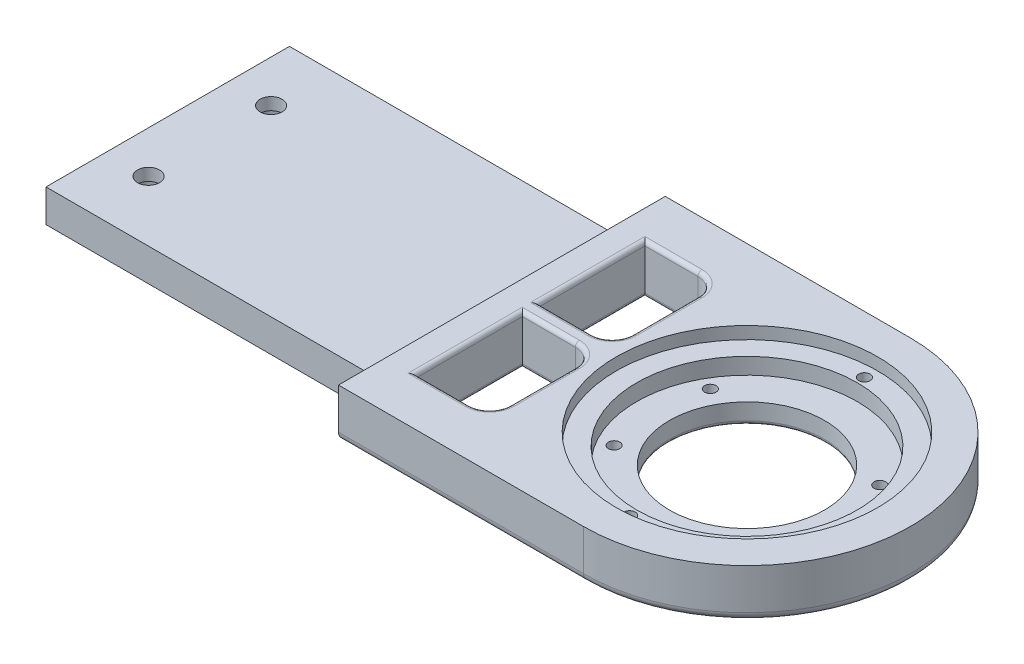
SolidWorks part; units mm, degrees
material "PLA"
ref_plane "Front Plane" through (0, 0, 0) normal (0, 0, 1) x (1, 0, 0)
ref_plane "Top Plane" through (0, 0, 0) normal (0, 1, 0) x (1, 0, 0)
ref_plane "Right Plane" through (0, 0, 0) normal (1, 0, 0) x (0, 0, -1)
sketch "Sketch1" plane through (0, 0, 0) normal (0, 1, 0) x (1, 0, 0)
  circle A0 centre (0, 0) radius 19
  circle A1 centre (0, 0) radius 40
  dimension "D1" = 38
  dimension "D2" = 80
extrude "Boss-Extrude1" add sketch "Sketch1" along normal blind 5
sketch "Sketch2" plane through (0, 5, 0) normal (0, 1, 0) x (1, 0, 0)
  circle A0 centre (0, 0) radius 27
  circle A1 centre (0, 0) radius 40
  dimension "D1" = 54
  dimension "D2" = 80
extrude "Boss-Extrude2" add sketch "Sketch2" along normal blind 4
sketch "Sketch3" plane through (0, 9, 0) normal (0, 1, 0) x (1, 0, 0)
  circle A0 centre (0, 0) radius 32
  circle A1 centre (0, 0) radius 40
  dimension "D1" = 64
  dimension "D2" = 80
extrude "Boss-Extrude3" add sketch "Sketch3" along normal blind 3
ref_plane "Plane1" through (-40, 0, 0) normal (-1, 0, 0) x (0, -1, 0)
sketch "Sketch6" plane through (-40, 0, 0) normal (-1, 0, 0) x (0, -1, 0)
  line L1 (-12, 40) -> (0, 40)
  line L2 (-12, 40) -> (-12, -40)
  line L3 (-12, -40) -> (0, -40)
  line L4 (0, 40) -> (0, -40)
extrude "Boss-Extrude4" add sketch "Sketch6" against normal up to surface and the other way blind 20 up to face at (0, 0, 40)
sketch "Sketch9" plane through (-60, 0, 0) normal (-1, 0, 0) x (0, 0, 1)
  line L1 (-30, 0) -> (30, 0)
  line L2 (-30, 0) -> (-30, 8)
  line L3 (-30, 8) -> (30, 8)
  line L4 (30, 0) -> (30, 8)
  line L5 (0, 12) -> (0, 0) construction
  line L6 (40, 12) -> (-40, 12) construction
  point P10 (0, 8)
  dimension "D1" = 8
  dimension "D2" = 60
extrude "Boss-Extrude5" add sketch "Sketch9" along normal blind 82
sketch "Sketch21" plane through (0, 12, 0) normal (0, 1, 0) x (1, 0, 0)
  line L0 (-60, 0) -> (0, 0) construction
  line L1 (-60, 40) -> (-20, 40)
  line L2 (-60, 40) -> (-60, 35)
  line L3 (-60, 35) -> (-20, 35)
  line L4 (-20, 40) -> (-20, 35)
  line L5 (-60, -30) -> (-60, 30) construction
  line L6 (-60, -35) -> (-20, -35)
  line L7 (-20, -40) -> (-20, -35)
  line L8 (-60, -40) -> (-20, -40)
  line L9 (-60, -40) -> (-60, -35)
  dimension "D1" = 5
  dimension "D2" = 40
extrude "Boss-Extrude6" [suppressed] add sketch "Sketch21" along normal blind 24.5
sketch "Sketch19" plane through (0, 0, 0) normal (0, -1, 0) x (1, 0, 0)
  line L0 (-60, 30) -> (-60, -30) construction
  line L1 (-60, 0) -> (0, 0) construction
  line L2 (-53, 28) -> (-35, 28)
  line L3 (-53, 28) -> (-53, 2)
  line L4 (-53, 2) -> (-35, 2)
  line L5 (-35, 28) -> (-35, 2)
  line L10 (-131.5, 30) -> (-131.5, -30) construction
  line L11 (-142, 30) -> (-60, 30) construction
  line L12 (-142, -30) -> (-60, -30) construction
  line L13 (-142, 15) -> (-131.5, 15) construction
  line L14 (-142, -30) -> (-142, 30) construction
  line L15 (-53, -2) -> (-35, -2)
  line L16 (-35, -28) -> (-35, -2)
  line L17 (-53, -28) -> (-35, -28)
  line L18 (-53, -28) -> (-53, -2)
  circle A0 centre (-131.5, 15) radius 2.7
  circle A2 centre (-131.5, -15) radius 2.7
  dimension "D12" = 5.4
  dimension "D2" = 7
  dimension "D3" = 18
  dimension "D4" = 26
  dimension "D5" = 2
  dimension "D8" = 10.5
  dimension "D9" = 15
extrude "Cut-Extrude8" cut sketch "Sketch19" against normal blind 12
sketch "Sketch5" plane through (0, 12, 0) normal (0, 1, 0) x (1, 0, 0)
  line L0 (0, 0) -> (-40, 0) construction
  line L1 (0, 0) -> (-0.2531, 28.9989) construction
  circle A0 centre (0, 0) radius 23.75 construction
  circle A1 centre (0, 0) radius 29 construction
  circle A2 centre (-0.2531, 28.9989) radius 1.4
  circle A3 centre (-0.2073, 23.7491) radius 1.375 construction
  circle A4 centre (24.9872, 14.7186) radius 1.4 construction
  circle A5 centre (20.4637, 12.054) radius 1.375
  circle A6 centre (25.2403, -14.2803) radius 1.4 construction
  circle A7 centre (20.6709, -11.6951) radius 1.375
  circle A8 centre (0.2531, -28.9989) radius 1.4
  circle A9 centre (0.2073, -23.7491) radius 1.375 construction
  circle A10 centre (-24.9872, -14.7186) radius 1.4 construction
  circle A11 centre (-20.4637, -12.054) radius 1.375
  circle A12 centre (-25.2403, 14.2803) radius 1.4 construction
  circle A13 centre (-20.6709, 11.6951) radius 1.375
  circle A14 centre (0, 0) radius 40 construction
  point P31 (0, 0)
  dimension "D1" = 47.5
  dimension "D2" = 58
  dimension "D3" = 2.75
  dimension "D4" = 2.8
  dimension "D6" = 89.5
  dimension "D5" = 6
extrude "Cut-Extrude1-Hole" cut sketch "Sketch5" against normal through all
sketch "Sketch22" plane through (0, 8, 0) normal (0, 1, 0) x (1, 0, 0)
  line L0 (-141.8, 29.8) -> (-141.8, -29.8)
  line L1 (-142, 30) -> (-60, 30)
  line L2 (-142, 30) -> (-142, -30)
  line L3 (-142, -30) -> (-60, -30)
  line L4 (-60, 30) -> (-60, 29.8)
  line L5 (-141.8, -29.8) -> (-60.2, -29.8)
  line L7 (-141.8, 29.8) -> (-60.2, 29.8)
  line L8 (-60.2, 29.8) -> (-60, 29.8)
  line L9 (-60.2, -29.8) -> (-60, -29.8)
  line L10 (-60, -29.8) -> (-60, -30)
  line L11 (-60, 30) -> (-60, -30) construction
  line L12 (-60.2, 29.8) -> (-60.2, -29.8) construction
  dimension "D1" = 0.2
extrude "Cut-Extrude9-Reality" cut sketch "Sketch22" against normal through all and the other way through all
hole_wizard "CBORE for M5 Hex Head Bolt1" positions "3DSketch2" profile "Sketch20" counterbore size "M5" standard "ANSI Metric"
sketch3d "3DSketch2"
  line L0 (-131.5, 8, 15) -> (-131.5, 0, 15) construction
  line L2 (-131.5, 8, -15) -> (-131.5, 0, -15) construction
  point P0 (-131.5, 0, 15)
  point P8 (-131.5, 0, -15)
sketch "Sketch20" plane through (-131.5, 0, 15) normal (1, 0, 0) x (0, 0, -1)
  line L0 (0, 0) -> (0, 17)
  line L1 (0, 17) -> (2.7, 17)
  line L2 (2.7, 17) -> (2.7, 5)
  line L3 (2.7, 5) -> (4.2, 5)
  line L4 (4.2, 5) -> (4.2, 0)
  line L5 (4.2, 0) -> (0, 0)
  line L10 (0, 17) -> (-2.7, 17) construction
  line L11 (0, -6.35) -> (0, 107.95) construction
  dimension "Hole Dia." = 5.4
  dimension "Hole Depth" = 17
  dimension "C'Bore Dia." = 8.4
  dimension "C'Bore Depth" = 5
  dimension "Drill Angle" = 180
hole_wizard "CSK for M2.5 Flat Head Machine Screw1" positions "3DSketch1" profile "Sketch8" countersink size "M2.5" standard "ANSI Metric" end condition through all
sketch3d "3DSketch1"
  line L0 (-20.4637, 0, 12.054) -> (-20.4637, 5, 12.054) construction
  line L1 (-20.6709, 0, -11.6951) -> (-20.6709, 5, -11.6951) construction
  line L2 (20.4637, 0, -12.054) -> (20.4637, 5, -12.054) construction
  line L3 (20.6709, 0, 11.6951) -> (20.6709, 5, 11.6951) construction
  line L4 (0.2531, 0, 28.9989) -> (0.2531, 9, 28.9989) construction
  line L5 (-0.2531, 0, -28.9989) -> (-0.2531, 9, -28.9989) construction
  point P0 (-20.4637, 0, 12.054)
  point P4 (-20.6709, 0, -11.6951)
  point P8 (20.4637, 0, -12.054)
  point P12 (20.6709, 0, 11.6951)
  point P17 (0.2531, 0, 28.9989)
  point P21 (-0.2531, 0, -28.9989)
sketch "Sketch8" plane through (-20.4637, 0, 12.054) normal (1, 0, 0) x (0, 0, -1)
  line L0 (0, 0) -> (0, 12)
  line L1 (0, 12) -> (1.4, 12)
  line L2 (1.4, 12) -> (1.4, 1.15)
  line L3 (1.4, 1.15) -> (2.55, 0)
  line L5 (2.55, 0) -> (0, 0)
  line L6 (-1.4, 1.15) -> (-2.55, 0) construction
  line L11 (0, -6.35) -> (0, 107.95) construction
  dimension "Thru Hole Dia." = 2.8
  dimension "Thru Hole Depth" = 12
  dimension "Near C'Sink Dia." = 5.1
  dimension "Near C'Sink Angle" = 90
fillet "Fillet1-5mm" radius 5 4 edges at (-35, 6, 2) (-35, 6, -2) (-35, 6, -28) (-35, 6, 28)
fillet "Fillet2-2mm" radius 2 3 edges at (-30, 0, 40) (-30, 0, -40) (40, 0, 0)
fillet "Fillet3-1mm" radius 1 25 edges at (0, 0, 19) (-46.5, 12, 2) (-36.4645, 12, 3.4645) (-46.5, 12, -2) (-36.4645, 12, -3.4645) (-35, 12, 15) (-35, 12, -15) (-53, 12, 15) (-53, 12, -15) (-46.5, 0, 2) (-36.4645, 0, 3.4645) (-46.5, 0, -2) (-36.4645, 0, -3.4645) (-53, 0, -15) (-53, 0, 15) (-35, 0, 15) (-35, 0, -15) (-46.5, 0, 28) (-36.4645, 0, 26.5355) (-46.5, 0, -28) (-36.4645, 0, -26.5355) (-46.5, 12, 28) (-36.4645, 12, 26.5355) (-46.5, 12, -28) (-36.4645, 12, -26.5355)
sketch "Sketch18" plane through (0, 0, 0) normal (0, -1, 0) x (1, 0, 0)
  line L1 (-54.8162, 36.3358) -> (17.8553, 36.3358)
  line L2 (-54.8162, 36.3358) -> (-54.8162, -44.4431)
  line L3 (-54.8162, -44.4431) -> (17.8553, -44.4431)
  line L4 (17.8553, 36.3358) -> (17.8553, -44.4431)
extrude "Cut-Extrude7" [suppressed] cut sketch "Sketch18" against normal blind 2
